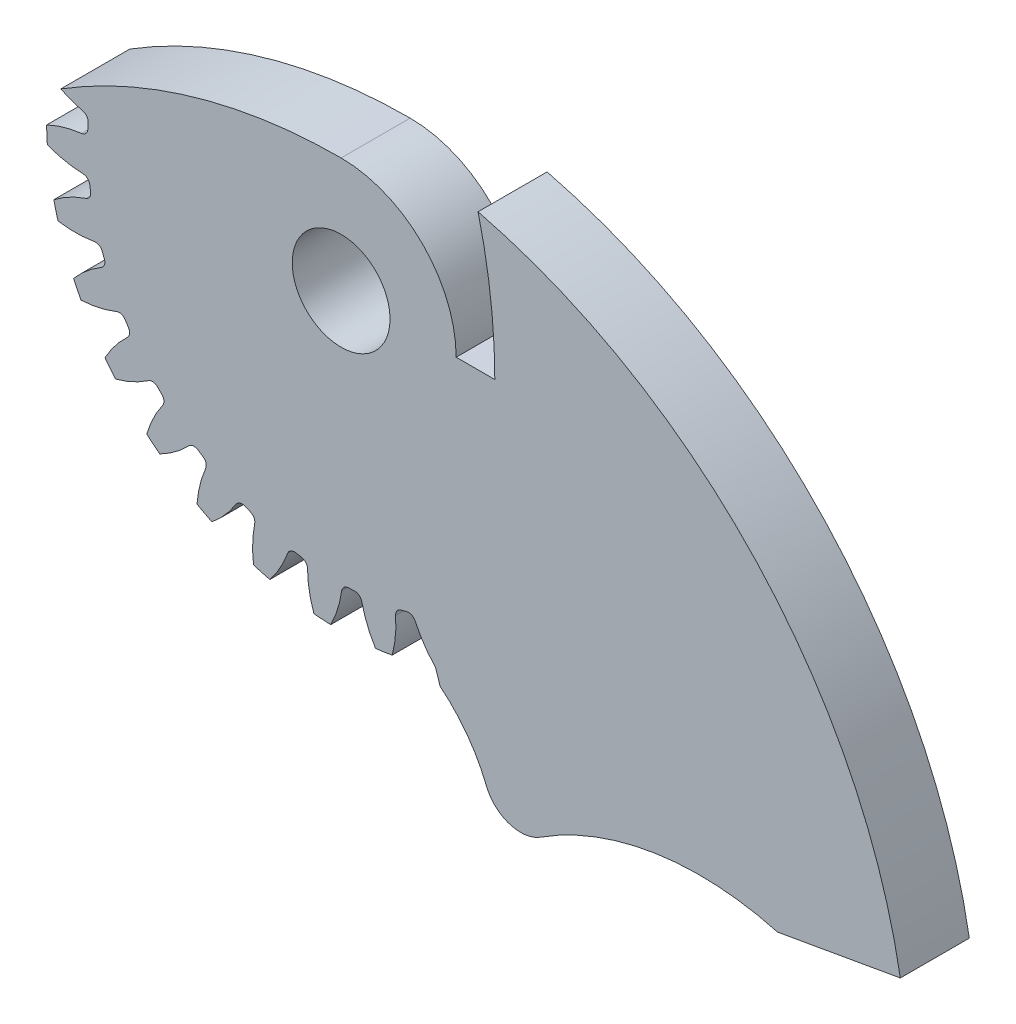
SolidWorks part; units mm, degrees
material "ABS"
ref_plane "Front" through (0, 0, 0) normal (0, 0, 1) x (1, 0, 0)
ref_plane "Top" through (0, 0, 0) normal (0, 1, 0) x (1, 0, 0)
ref_plane "Right" through (0, 0, 0) normal (1, 0, 0) x (0, 0, -1)
sketch "Sketch3" plane through (0, 0, 0) normal (0, 0, 1) x (1, 0, 0)
  circle A0 centre (0, 0) radius 40.64
  dimension "od" = 81.28
extrude "gearBody" add sketch "Sketch3" along normal blind 9.525
sketch "Sketch2" plane through (0, 0, 0) normal (0, 0, 1) x (1, 0, 0)
  line L0 (0, 0) -> (34.0786, 14.1158) construction
  line L1 (45.4751, -11.4855) -> (0, 0) construction
  line L2 (0, 0) -> (36.3143, 0) construction
  line L3 (38.0972, -0.458) -> (37.8451, -4.4001) construction
  line L5 (37.9712, -2.4291) -> (0, 0) construction
  line L7 (0, 0) -> (36.8864, 0) construction
  arc A0 (36.879, -0.7403) -> (36.6727, -3.9649) centre (0, 0) ccw construction
  arc A1 (40.637, 0.4947) -> (40.2427, -5.6687) centre (0, 0) ccw construction
  arc A2 (38.0972, -0.458) -> (37.8451, -4.4001) centre (0, 0) ccw construction
  arc A3 (34.9015, -2.6404) -> (34.9534, -1.8283) centre (0, 0) ccw
  arc A4 (45.4751, -11.4855) -> (35.6466, -3.6712) centre (32.0022, -18.3431) ccw
  arc A5 (45.4751, -11.4855) -> (46.5679, 5.5974) centre (0, 0) ccw
  arc A6 (46.5679, 5.5974) -> (35.8238, -0.9008) centre (34.0786, 14.1158) cw
  arc A7 (34.9534, -1.8283) -> (35.8238, -0.9008) centre (35.9376, -1.8798) cw
  arc A8 (35.6466, -3.6712) -> (34.9015, -2.6404) centre (35.8842, -2.7147) cw
  point P6 (46.5679, 5.5974)
  point P22 (45.4751, -11.4855)
  dimension "baseDia" = 73.7729
  dimension "od" = 81.28
  dimension "pd" = 76.2
  dimension "rd" = 70.0024
  dimension "rFillet" = 0.9855
  dimension "pointX" = 46.5679
  dimension "pointY" = 5.5974
  dimension "CTT" = 3.9421
  dimension "flankCenterAngle" = 22.5
extrude "toothCut" cut sketch "Sketch2" along normal through all
pattern_circular "CirPattern1" count 30 over 360 about axis through (0, 0, 9.525) along (0, 0, -1) of "toothCut"
sketch "hub1Dia" plane through (0, 0, 0) normal (0, 0, -1) x (-1, 0, 0)
  circle A0 centre (0, 0) radius 12.7
  dimension "hub1Dia" = 25.4
sketch "hub2Dia" plane through (0, 0, 9.525) normal (0, 0, 1) x (1, 0, 0)
  circle A0 centre (0, 0) radius 12.7
  dimension "hub2dia" = 25.4
sketch "boreDia" plane through (0, 0, 0) normal (0, 0, 1) x (1, 0, 0)
  circle A0 centre (0, 0) radius 6.7469
  dimension "boreDia" = 13.4937
extrude "bore" cut sketch "boreDia" against normal mid plane 25400
sketch "Sketch4" plane through (0, 0, 9.525) normal (0, 0, 1) x (1, 0, 0)
  circle A0 centre (0, -57.15) radius 78.359
  arc A2 (-42.9159, 8.4119) -> (42.9159, 8.4119) centre (0, 0) cw
  dimension "D1" = 156.718
  dimension "D2" = 57.15
extrude "Cut-Extrude1" cut sketch "Sketch4" against normal through all contours A0 region at (0, 27.8712, 9.525)
sketch "Sketch5" plane through (0, 0, 9.525) normal (0, 0, 1) x (1, 0, 0)
  line L0 (0, 21.209) -> (21.5163, 7.6712)
  line L1 (21.5163, 7.6712) -> (8.9608, -26.928)
  line L2 (8.9608, -26.928) -> (13.028, -38.4952)
  line L3 (0, 0) -> (0, -57.15) construction
  line L4 (0, -57.15) -> (-49.4328, 3.6491) construction
  line L5 (0, -57.15) -> (67.8609, -96.3295) construction
  line L6 (13.6543, -40.4261) -> (13.028, -38.4952)
  line L9 (0, -57.15) -> (77.1686, -43.5431) construction
  line L12 (60.232, -46.5295) -> (77.1686, -43.5431)
  circle A1 centre (0, -57.15) radius 78.359 construction
  arc A5 (0, 21.209) -> (77.1686, -43.5431) centre (0, -57.15) cw
  circle A6 centre (0, -57.15) radius 21.59 construction
  arc A10 (20.0525, -49.1485) -> (13.6543, -40.4261) centre (0, -57.15) ccw
  circle A12 centre (49.4934, -85.725) radius 40.64 construction
  arc A13 (27.5177, -51.539) -> (60.232, -46.5295) centre (49.4934, -85.725) cw
  arc A14 (27.5177, -51.539) -> (20.0525, -49.1485) centre (24.7708, -47.2658) cw
  point P28 (21.569, -56.1981)
  dimension "D1" = 43.18
  dimension "D3" = 81.28
  dimension "D7" = 5.08
  dimension "D6" = 156.718
  dimension "D2" = 120
  dimension "D4" = 57.15
  dimension "D5" = 80
extrude "Boss-Extrude1" add sketch "Sketch5" against normal up to surface (9.525 mm away) up to face at (6.7469, 0, 0)
sketch "Sketch6" plane through (0, 0, 9.525) normal (0, 0, 1) x (1, 0, 0)
  line L1 (-41.2829, 3.086) -> (-43.5386, 8)
  line L2 (15.875, 0) -> (21.209, 0)
  circle A0 centre (0, -57.15) radius 78.359 construction
  arc A1 (77.1686, -43.5431) -> (-36.286, 12.3011) centre (0, -57.15) ccw construction
  circle A2 centre (0, 0) radius 15.875 construction
  arc A3 (0, 15.875) -> (15.875, 0) centre (0, 0) cw
  arc A4 (18.8964, 18.8964) -> (-43.5386, 8) centre (0, -57.15) ccw
  arc A5 (0, 15.875) -> (-41.2829, 3.086) centre (0, -57.15) ccw
  circle A6 centre (0, 0) radius 21.209 construction
  circle A8 centre (-57.15, 0) radius 78.359 construction
  arc A9 (21.209, 0) -> (18.8964, 18.8964) centre (-57.15, 0) ccw
  dimension "D4" = 57.15
  dimension "D1" = 31.75
  dimension "D2" = 42.418
  dimension "D3" = 156.718
extrude "Cut-Extrude2" cut sketch "Sketch6" against normal through all
equation "\"Bodytube_OD\" = 6.17in"
equation "\"Bodytube_ID\" = 5.998in"
equation "\"Fwd_Tube_Length\" = 40in"
equation "\"Mid_Tube_Length\" = 1in"
equation "\"Aft_Section_Length\"= 39in"
equation "\"Mid_Coupler_Length\"= 13in"
equation "\"Aft_Lower_Length\"= 22in"
equation "\"AB_Coupler_OD_Length\"= 1in"
equation "\"AB_Coupling_Section_Length\"= 0.375in"
equation "\"AB_Coupler_Length\"= \"AB_Coupler_OD_Length\" + \"AB_Coupling_Section_Length\" * 2"
equation "\"Cutout_Angle\" = 80"
equation "\"AB_Paddle_Height\" = 0.375in"
equation "\"AB_Coupler_Num_Screws\"= 6"
equation "\"Num_Cutouts\" = 3"
equation "\"AB_Coupler_OD\"= 6.17in"
equation "\"AB_Coupler_ID\"= 5.75in"
equation "\"AB_Coupler_Surface_Diameter\"= 5.998in"
equation "\"AB_Coupling_Screw_Diameter\"= 0.1065in"
equation "\"AB_Central_Bushing_Length\" = .75in"
equation "\"Lead_Screw_Dist\" = 2.25in"
equation "\"Lead_Screw_Diam\" = (27/64)*1in"
equation "\"Lead_Screw_Length\" = (\"Mid_Coupler_Length\" + 2*0.375in + 2*0.5in)"
equation "\"Paddle_Pin_Offset\" = .25in"
equation "\"Paddle_Pin_Radius\" = 2.25in"
equation "\"Fwd_BKHD_From_Top\" = 18in"
equation "\"D1@Sketch4\"=\"Bodytube_OD\""
equation "\"D2@Sketch4\"=\"Paddle_Pin_Radius\""
equation "\"D3@Sketch5\"=\"Paddle_Gear_OD\""
equation "\"D4@Sketch5\"=\"Paddle_Pin_Radius\""
equation "\"Motor_OD\" = 4in"
equation "\"Aft_Upper_Length\"= \"Aft_Section_Length\" - \"Aft_Lower_Length\" - \"AB_Coupler_OD_Length\""
equation "\"Paddle_Gear_OD\" = 3.2in"
equation "\"D5@Sketch5\"=\"Cutout_Angle\""
equation "\"D6@Sketch5\"=\"Bodytube_OD\""
equation "\"D1@Sketch6\"=\"AB_Coupler_ID\"-2*\"Paddle_Pin_Radius\""
equation "\"D2@Sketch6\"=\"Bodytube_OD\"-2*\"Paddle_Pin_Radius\""
equation "\"D3@Sketch6\"=\"Bodytube_OD\""
equation "\"D4@Sketch6\"=\"Paddle_Pin_Radius\""
